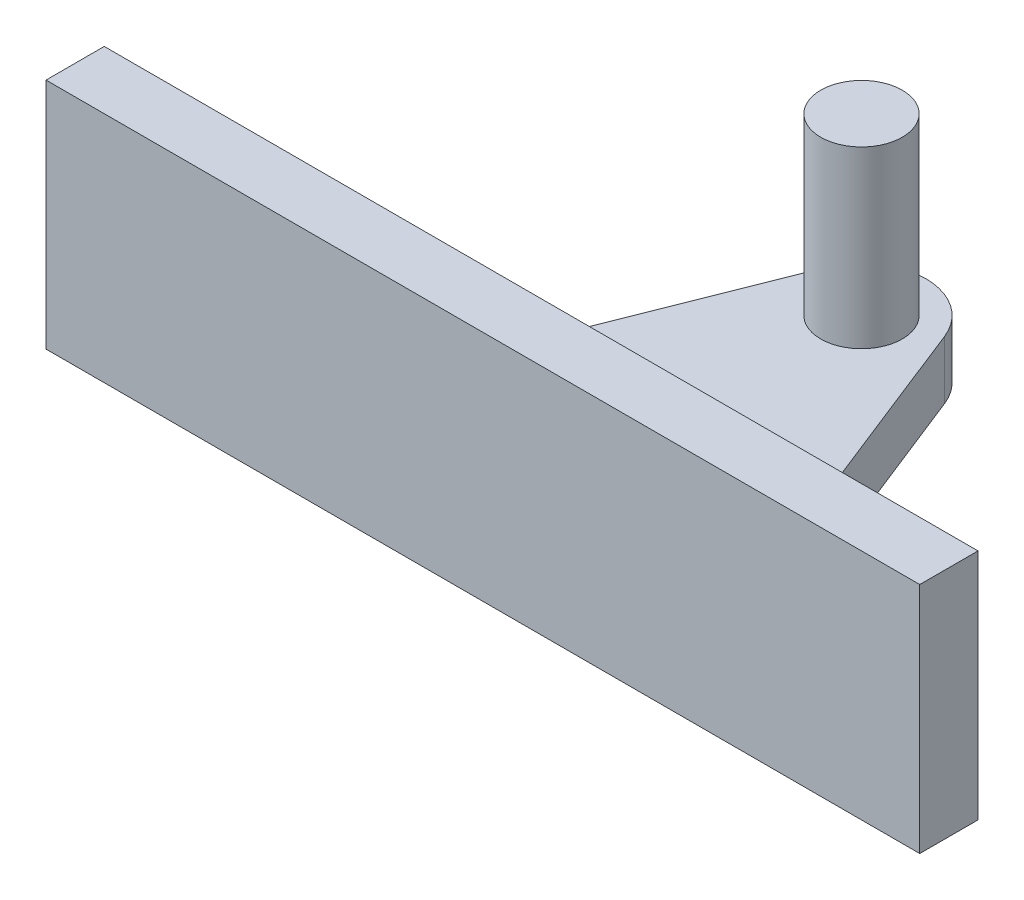
SolidWorks part; units mm, degrees
ref_plane "Front Plane" through (0, 0, 0) normal (0, 0, 1) x (1, 0, 0)
ref_plane "Top Plane" through (0, 0, 0) normal (0, 1, 0) x (1, 0, 0)
ref_plane "Right Plane" through (0, 0, 0) normal (1, 0, 0) x (0, 0, -1)
sketch "Sketch1" plane through (0, 0, 0) normal (0, 1, 0) x (1, 0, 0)
  line L0 (-10.2309, 4.0409) -> (-37.5, -65)
  line L1 (-37.5, -65) -> (37.5, -65)
  line L2 (37.5, -65) -> (10.2309, 4.0409)
  line L4 (-75, -65) -> (75, -65)
  line L5 (-75, -65) -> (-75, -55)
  line L6 (-75, -55) -> (75, -55)
  line L7 (75, -65) -> (75, -55)
  circle A0 centre (0, 0) radius 7
  circle A1 centre (0, 0) radius 11
  point P7 (0, -65)
  point P10 (0, -55)
  dimension "D1" = 14
  dimension "D3" = 65
  dimension "D4" = 75
  dimension "D5" = 10
  dimension "D6" = 150
  dimension "D2" = 4
extrude "Boss-Extrude1" add sketch "Sketch1" along normal blind 10 contours A1 L0 L6 L2 | A1 A0 | L4 L7 L6 L2 | L6 L0 L1 L2 | L6 L5 L4 L0 | A0 region at (0, 0, 34.0975) region at (0, 0, -10.6889) region at (0, 0, 60.0927) region at (-55.2461, 0, 59.9166) region at (55.2461, 0, 59.9166) region at (0, 0, 0)
extrude "Boss-Extrude2" add sketch "Sketch1<3>" along normal blind 30 from surface contours A0 | L6 L5 L4 L0 | L4 L7 L6 L5 region at (-55.2461, 0, 59.9166) region at (0, 0, 0) starting at face at (0, 10, 41.8699)
sketch "Sketch1<3>" plane through (0, 0, 0) normal (0, 1, 0) x (1, 0, 0) same geometry as "Sketch1"
fillet "Fillet1" radius 10 3 edges at (-33.5503, 5, 55) (0, 10, 55) (33.5503, 5, 55)
